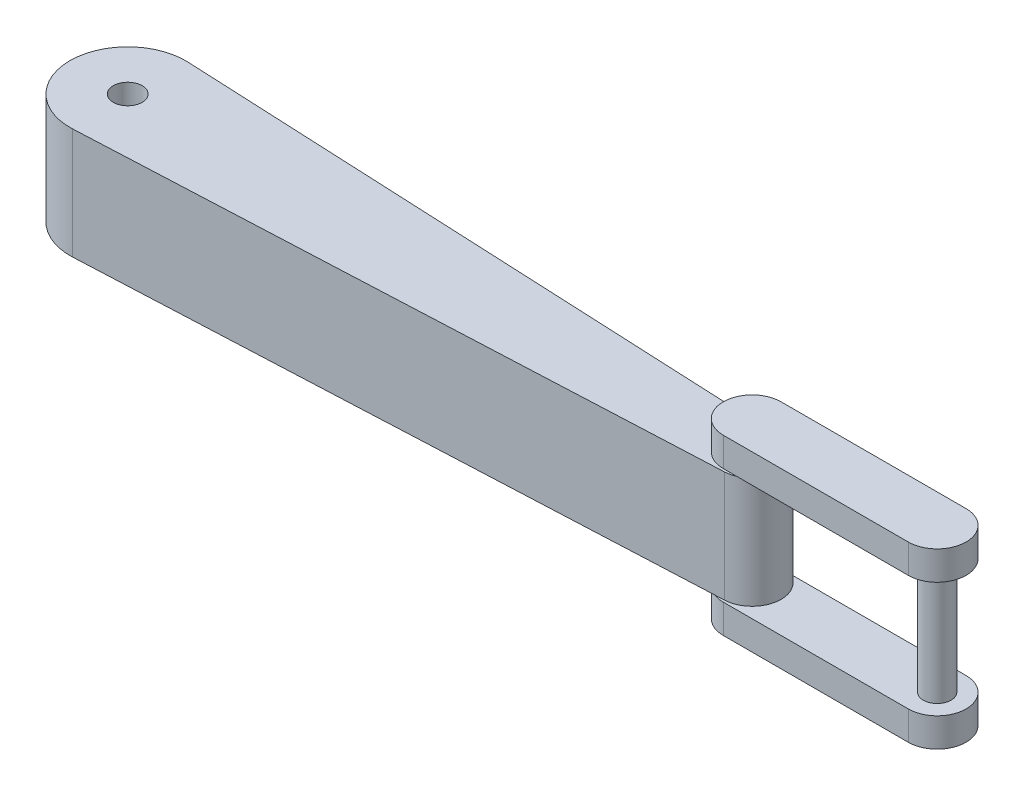
SolidWorks part; units mm, degrees
ref_plane "Front Plane" through (0, 0, 0) normal (0, 0, 1) x (1, 0, 0)
ref_plane "Top Plane" through (0, 0, 0) normal (0, 1, 0) x (1, 0, 0)
ref_plane "Right Plane" through (0, 0, 0) normal (1, 0, 0) x (0, 0, -1)
sketch "Sketch2" plane through (0, 0, 0) normal (0, 1, 0) x (1, 0, 0)
  line L0 (0, 0) -> (270, 0) construction
  line L1 (270.5787, 12.4866) -> (1.1574, 24.9732)
  line L2 (270.5787, -12.4866) -> (1.1574, -24.9732)
  arc A0 (1.1574, 24.9732) -> (1.1574, -24.9732) centre (0, 0) ccw
  arc A1 (270.5787, -12.4866) -> (270.5787, 12.4866) centre (270, 0) ccw
  circle A2 centre (0, 0) radius 6.25
  dimension "D1" = 12.5
  dimension "D3" = 25
  dimension "D4" = 12.5
  dimension "D2" = 270
extrude "Boss-Extrude1" add sketch "Sketch2" along normal blind 24 and the other way blind 24
sketch "Sketch3" plane through (0, 24, 0) normal (0, 1, 0) x (1, 0, 0)
  line L1 (270, 12.5) -> (350, 12.5)
  line L2 (270, -12.5) -> (350, -12.5)
  arc A0 (270, 12.5) -> (270, -12.5) centre (270, 0) ccw
  arc A1 (350, -12.5) -> (350, 12.5) centre (350, 0) ccw
  dimension "D1" = 25
  dimension "D2" = 25
  dimension "D3" = 80
extrude "Boss-Extrude2" add sketch "Sketch3" along normal blind 12.5 from offset 1
sketch "Sketch5" plane through (0, -24, 0) normal (0, -1, 0) x (1, 0, 0)
  line L2 (270.5787, 12.4866) -> (1.1574, 24.9732)
  line L3 (1.1574, -24.9732) -> (270.5787, -12.4866)
  line L4 (270.5787, 12.4866) -> (1.1574, 24.9732) construction
  line L5 (1.1574, -24.9732) -> (270.5787, -12.4866) construction
  circle A0 centre (270, 0) radius 5
  arc A2 (270.5787, -12.4866) -> (270.5787, 12.4866) centre (270, 0) ccw
  arc A3 (1.1574, 24.9732) -> (1.1574, -24.9732) centre (0, 0) ccw
  arc A4 (270.5787, -12.4866) -> (270.5787, 12.4866) centre (270, 0) ccw construction
  arc A5 (1.1574, 24.9732) -> (1.1574, -24.9732) centre (0, 0) ccw construction
  dimension "D1" = 0
extrude "Boss-Extrude4" add sketch "Sketch5" along normal blind 10 and the other way blind 54
mirror "Mirror1" about plane through (0, 0, 0) normal (0, 1, 0) of "Boss-Extrude2"
sketch "Sketch6" plane through (0, 0, 0) normal (0, 1, 0) x (1, 0, 0)
  line L2 (350, 12.5) -> (270, 12.5)
  line L3 (270, -12.5) -> (350, -12.5)
  line L4 (350, 12.5) -> (270, 12.5) construction
  line L5 (270, -12.5) -> (350, -12.5) construction
  circle A0 centre (350, 0) radius 6
  arc A2 (270, 12.5) -> (270, -12.5) centre (270, 0) ccw
  arc A3 (350, -12.5) -> (350, 12.5) centre (350, 0) ccw
  arc A4 (270, 12.5) -> (270, -12.5) centre (270, 0) ccw construction
  arc A5 (350, -12.5) -> (350, 12.5) centre (350, 0) ccw construction
  dimension "D2" = 12
  dimension "D1" = 0
extrude "Boss-Extrude5" add sketch "Sketch6" along normal blind 31 and the other way blind 30
